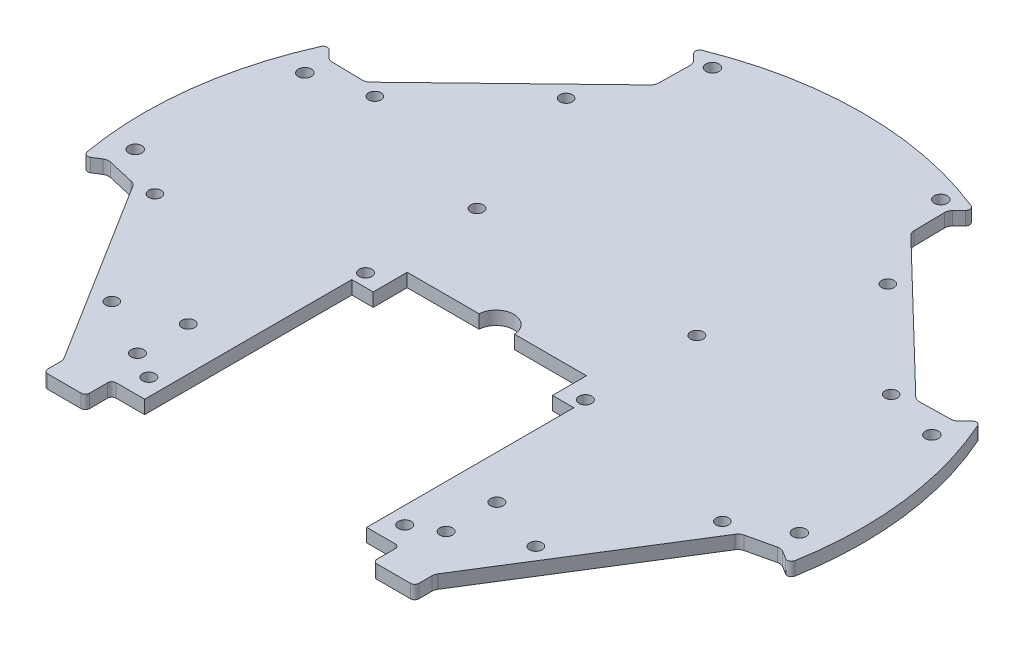
SolidWorks part; units mm, degrees
note: '?' marks a value the reader was unsure of.
material "6061 Alloy"
ref_plane "Front Plane" through (0, 0, 0) normal (0, 0, 1) x (1, 0, 0)
ref_plane "Top Plane" through (0, 0, 0) normal (0, 1, 0) x (1, 0, 0)
ref_plane "Right Plane" through (0, 0, 0) normal (1, 0, 0) x (0, 0, -1)
sketch "Sketch1" plane through (0, 0, 0) normal (0, 1, 0) x (1, 0, 0)
  line L0 (0, 0) -> (0, -59.55) construction
  line L1 (-83.4462, -16.178) -> (-71.2857, -8.5793) construction
  line L6 (0, 0) -> (-59.046, 61.1439) construction
  line L7 (0, 0) -> (-72.0841, -45.0431) construction
  line L8 (-33.174, 78.2591) -> (-23.2129, 67.9442) construction
  line L9 (-72.0841, -45.0431) -> (-70.388, -43.9833) construction
  line L10 (-70.388, -43.9833) -> (-84.9608, -20.662) construction
  line L11 (-84.9608, -20.662) -> (-72.2401, -12.7132) construction
  line L12 (-72.2401, -12.7132) -> (-43.0945, -59.3558) construction
  line L13 (-43.0945, -59.3558) -> (-55.8152, -67.3046) construction
  line L14 (-55.8152, -67.3046) -> (-70.388, -43.9833) construction
  line L21 (-59.046, 61.1439) -> (-57.6566, 59.7052)
  line L22 (-77.4385, 40.6021) -> (-37.8748, 78.8083) construction
  line L23 (-73.9694, 32.6911) -> (-77.0537, 35.885)
  line L24 (-37.8748, 78.8083) -> (-27.4549, 68.0182) construction
  line L25 (-27.4549, 68.0182) -> (-67.0186, 29.812) construction
  line L26 (-67.0186, 29.812) -> (-77.4385, 40.6021) construction
  line L27 (-43.0945, -64.8266) -> (-34, -64.8266)
  line L33 (-86.5505, -18.1178) -> (-71.2857, -8.5793) construction
  line L34 (0, 0) -> (0, 50000) construction
  line L35 (0, 0) -> (-50000, 0) construction
  line L36 (-60.6531, -59.55) -> (-19.8595, -59.55) construction
  line L38 (-67.0927, 25.57) -> (-79.5965, 38.5181) construction
  line L39 (-54.9774, -64.8266) -> (0, -64.8266) construction
  line L40 (-35.7168, 80.8923) -> (-23.2129, 67.9442) construction
  line L41 (-38.9606, -60.3102) -> (-54.2255, -69.8488) construction
  line L42 (-34, -59.55) -> (-19.8595, -59.55) construction
  line L43 (-43.0945, -64.8266) -> (-43.0945, -58.4123) construction
  line L45 (73.9694, 32.6911) -> (77.0537, 35.885)
  line L46 (-71.2857, -8.5793) -> (-38.9606, -60.3102) construction
  line L47 (83.4462, -16.178) -> (79.6809, -13.8252)
  line L48 (69.4846, -16.1792) -> (43.8945, -57.132)
  line L50 (43.0945, -64.8266) -> (34, -64.8266)
  line L51 (34, -59.55) -> (34, -64.8266)
  line L52 (0, 0) -> (72.0841, -45.0431) construction
  line L53 (0, 0) -> (59.046, 61.1439) construction
  line L54 (-30.0897, 75.0653) -> (-30.2847, 63.8954)
  line L55 (-62.7996, 32.4961) -> (-30.2847, 63.8954)
  line L56 (-30.0897, 75.0653) -> (-33.174, 78.2591)
  line L57 (73.9694, 32.6911) -> (77.0537, 35.885)
  line L58 (30.0897, 75.0653) -> (33.174, 78.2591)
  line L59 (-34, -59.55) -> (-34, -58.55)
  line L60 (62.7996, 32.4961) -> (30.2847, 63.8954)
  line L61 (-73.9694, 32.6911) -> (-62.7996, 32.4961)
  line L62 (-77.0537, 35.885) -> (-67.0927, 25.57) construction
  line L63 (-83.4462, -16.178) -> (-79.6809, -13.8252)
  line L64 (-79.6809, -13.8252) -> (-69.4846, -16.1792)
  line L65 (-69.4846, -16.1792) -> (-43.8945, -57.132)
  line L66 (-27.4549, 68.0182) -> (-23.2129, 67.9442) construction
  line L67 (-72.2401, -12.7132) -> (-71.2857, -8.5793) construction
  line L68 (30.0897, 75.0653) -> (30.2847, 63.8954)
  line L69 (73.9694, 32.6911) -> (62.7996, 32.4961)
  line L70 (-34, -59.55) -> (-34, -64.8266)
  line L71 (79.6809, -13.8252) -> (69.4846, -16.1792)
  line L72 (-34, -58.55) -> (-20, -58.55)
  line L73 (-20, -58.55) -> (-19.8595, -59.55)
  line L74 (-19.8595, -59.55) -> (19.8595, -59.55)
  line L75 (20, -58.55) -> (19.8595, -59.55)
  line L76 (34, -58.55) -> (20, -58.55)
  line L77 (34, -59.55) -> (34, -58.55)
  line L78 (-43.0945, -64.8266) -> (-43.8945, -64.8266)
  line L79 (-19.8595, -59.55) -> (0, -59.55) construction
  line L80 (-19.8595, -59.55) -> (34, -59.55) construction
  line L81 (-43.8945, -64.8266) -> (-43.8945, -57.132)
  line L82 (-43.0945, -58.4123) -> (-43.8945, -57.132) construction
  line L83 (43.8945, -64.8266) -> (43.8945, -57.132)
  line L84 (43.0945, -64.8266) -> (43.8945, -64.8266)
  line L97 (-23.2129, 67.9442) -> (-67.0927, 25.57) construction
  circle A0 centre (0, 0) radius 85 construction
  circle A1 centre (0, 0) radius 90 construction
  arc A51 (-77.0537, 35.885) -> (-83.4462, -16.178) centre (0, 0) ccw
  arc A52 (77.0537, 35.885) -> (83.4462, -16.178) centre (0, 0) cw
  arc A54 (-33.174, 78.2591) -> (33.174, 78.2591) centre (0, 0) cw
  point P29 (-31.6318, 76.6622)
  point P33 (-47.2368, 48.9151)
  point P34 (31.6318, 76.6622)
  point P35 (-57.6673, -36.0345)
  point P85 (-57.6566, 59.7052)
  dimension "D2" = 58
  dimension "D10" = 82
  dimension "D12" = 170
  dimension "D14" = 34
  dimension "D13" = 1
  dimension "D15" = 3
  dimension "D3" = 180
  dimension "D4" = 64.8266
  dimension "D5" = 44
  dimension "D6" = 15
  dimension "D7" = 55
  dimension "D8" = 59.55
  dimension "D9" = 2
  dimension "D11" = 2
  dimension "D16" = 7
  dimension "D17" = 7
  dimension "D18" = 0.5
  dimension "D19" = 1
  dimension "D20" = 14
  dimension "D21" = 0.8
extrude "Boss-Extrude4" add sketch "Sketch1" along normal mid plane 3.175
ref_point "Rear_Axle_Center (L)"
ref_axis "Rear_Axle_Proj (L)" through (46.5421, 0, -48.1958) along (0, 1, 0)?
ref_point "Front_Axle_Center (L)"
ref_axis "Front_Axle_Proj (L)" through (57.2432, 0, 35.7696) along (0, 1, 0)?
ref_point "Front_Axle_Center (R)"
ref_axis "Front_Axle_Proj (R)" through (-57.2432, 0, 35.7696) along (0, 1, 0)?
ref_point "Read_Axle_Center (R)"
ref_axis "Rear_Axle_Proj (R)" through (-46.5421, 0, -48.1958) along (0, 1, 0)?
sketch "Sketch17" plane through (0, 1.5875, 0) normal (0, 1, 0) x (1, 0, 0)
  line L0 (0, -54.55) -> (0, -59.55) construction
  line L1 (-19.8595, -59.55) -> (19.8595, -59.55) construction
  circle A0 centre (0, -54.55) radius 8.5
  dimension "D1" = 17
  dimension "D2" = 5
extrude "Boss-Extrude5" [suppressed] add sketch "Sketch17" against normal up to surface (3.175 mm away)
ref_plane "Plane1" through (0, 0, 10) normal (0, 0, 1) x (1, 0, 0)
hole_wizard "M3 Clearance Hole3" positions "Sketch18" profile "Sketch19" hole size "M3" standard "ANSI Metric" end condition through all
sketch "Sketch18" plane through (0, -1.5875, 0) normal (0, -1, 0) x (-1, 0, 0)
  line L0 (-36.5, -50) -> (-36.5, -38) construction
  line L3 (0, 0) -> (0, -38) construction
  line L4 (36.5, -50) -> (36.5, -38) construction
  line L6 (0, -38) -> (36.5, -38) construction
  line L8 (0, -38) -> (-36.5, -38) construction
  line L9 (-36.5, -44) -> (36.5, -44) construction
  line L10 (0, -44) -> (0, 0) construction
  point P1 (36.5, -50)
  point P3 (36.5, -38)
  point P5 (-36.5, -50)
  point P33 (-36.5, -38)
  dimension "D1" = 12
  dimension "D2" = 73
  dimension "D4" = 38
sketch "Sketch19" plane through (-36.5, -1.5875, 50) normal (1, 0, 0) x (0, 0, -1)
  line L0 (0, 0) -> (0, 3.175)
  line L1 (0, 3.175) -> (1.5, 3.175)
  line L2 (1.5, 3.175) -> (1.5, 0)
  line L5 (1.5, 0) -> (0, 0)
  line L11 (0, -6.35) -> (0, 107.95) construction
  dimension "Thru Hole Dia." = 3
  dimension "Thru Hole Depth" = 3.175
hole_wizard "M3 Clearance Hole1" positions "Sketch11" profile "Sketch12" hole size "M3" standard "ANSI Metric" end condition through all
sketch "Sketch11" plane through (0, 1.5875, 0) normal (0, 1, 0) x (1, 0, 0)
  line L0 (83.4462, -16.178) -> (79.6809, -13.8252) construction
  line L2 (73.9694, 32.6911) -> (77.0537, 35.885) construction
  line L4 (-73.9694, 32.6911) -> (-77.0537, 35.885) construction
  line L6 (0, 0) -> (0, -50000) construction
  line L7 (78.4111, 9.6277) -> (84.3664, 10.3589) construction
  line L10 (74.155, 27.2403) -> (78.5423, -8.4914) construction
  line L12 (78.4111, 9.6277) -> (76.3487, 9.3744) construction
  arc A7 (77.964, -12.7523) -> (72.563, 31.2347) centre (0, 0) ccw construction
  arc A13 (-77.964, -12.7523) -> (-72.563, 31.2347) centre (0, 0) cw construction
  arc A17 (83.4462, -16.178) -> (77.0537, 35.885) centre (0, 0) ccw construction
  point P34 (78.5423, -8.4914)
  point P66 (74.155, 27.2403)
  point P70 (-74.155, 27.2403)
  point P71 (-78.5423, -8.4914)
  dimension "D1" = 6
  dimension "D2" = 36
sketch "Sketch12" plane through (-78.5423, 1.5875, 8.4914) normal (1, 0, 0) x (0, 0, 1)
  line L0 (0, 0) -> (0, 3.175)
  line L1 (0, 3.175) -> (1.55, 3.175)
  line L2 (1.55, 3.175) -> (1.55, 0)
  line L5 (1.55, 0) -> (0, 0)
  line L11 (0, -6.35) -> (0, 107.95) construction
  dimension "Thru Hole Dia." = 3.1
  dimension "Thru Hole Depth" = 3.175
hole_wizard "M3 Clearance Hole4" positions "Sketch9" profile "Sketch10" hole size "M3" standard "ANSI Metric" end condition through all
sketch "Sketch9" plane through (0, -1.5875, 0) normal (0, -1, 0) x (-1, 0, 0)
  line L0 (0, 0) -> (0, 63.4318) construction
  line L1 (-38.0437, 52.9272) -> (38.0437, 52.9272) construction
  line L3 (61.0625, 30.6981) -> (-61.0625, 30.6981) construction
  line L4 (-67.0993, -15.2789) -> (67.0993, -15.2789) construction
  line L5 (50.1419, -42.4164) -> (-50.1419, -42.4164) construction
  line L6 (-61.0625, 30.6981) -> (-38.0437, 52.9272) construction
  line L7 (38.0437, 52.9272) -> (61.0625, 30.6981) construction
  line L8 (67.0993, -15.2789) -> (50.1419, -42.4164) construction
  line L9 (-50.1419, -42.4164) -> (-67.0993, -15.2789) construction
  line L10 (0, 0) -> (-44.8055, 46.3974) construction
  line L11 (0, 0) -> (44.8055, 46.3974) construction
  line L12 (0, 0) -> (-96.9468, 0) construction
  line L14 (-55.1231, -34.4448) -> (0, 0) construction
  line L15 (0, 0) -> (55.1231, -34.4448) construction
  line L18 (-69.4846, -16.1792) -> (-43.8945, -57.132) construction
  line L19 (-62.7996, 32.4961) -> (-30.2847, 63.8954) construction
  point P0 (-67.0993, -15.2789)
  point P2 (-50.1419, -42.4164)
  point P9 (-61.0625, 30.6981)
  point P11 (-38.0437, 52.9272)
  point P30 (50.1419, -42.4164)
  point P31 (67.0993, -15.2789)
  point P32 (38.0437, 52.9272)
  point P33 (61.0625, 30.6981)
  dimension "D9" = 46
  dimension "D10" = 46
  dimension "D11" = 32
  dimension "D12" = 32
  dimension "D7" = 58
  dimension "D5" = 32
  dimension "D6" = 2.5
  dimension "D8" = 9.4
  dimension "D2" = 44
  dimension "D3" = 32
  dimension "D4" = 2.5
  dimension "D13" = 9.4
sketch "Sketch10" plane through (67.0993, -1.5875, 15.2789) normal (1, 0, 0) x (0, 0, -1)
  line L0 (0, 0) -> (0, 3.175)
  line L1 (0, 3.175) -> (1.475, 3.175)
  line L2 (1.475, 3.175) -> (1.475, 0)
  line L5 (1.475, 0) -> (0, 0)
  line L11 (0, -6.35) -> (0, 107.95) construction
  dimension "Thru Hole Dia." = 2.95
  dimension "Thru Hole Depth" = 3.175
hole_wizard "M3 Clearance Hole2" positions "Sketch13" profile "Sketch14" hole size "M3" standard "ANSI Metric" end condition through all
sketch "Sketch13" plane through (0, 1.5875, 0) normal (0, 1, 0) x (1, 0, 0)
  line L0 (0, 0) -> (0, 85) construction
  line L2 (-24, 47) -> (-24, 81) construction
  line L3 (-24, 47) -> (24, 47) construction
  line L4 (-24, 81) -> (24, 81) construction
  line L5 (24, 47) -> (24, 81) construction
  line L6 (-24, 47) -> (24, 81) construction
  line L7 (-24, 81) -> (24, 47) construction
  line L8 (-38.0437, 52.9272) -> (-61.0625, 30.6981) construction
  line L10 (-36.307, 51.1289) -> (-59.3259, 28.8998) construction
  line L11 (-16.3488, 39.8187) -> (-31.6313, 55.6441) construction
  line L12 (-16.3488, 39.8187) -> (-48.7191, 8.559) construction
  line L13 (-31.6313, 55.6441) -> (-64.0016, 24.3845) construction
  line L14 (-48.7191, 8.559) -> (-64.0016, 24.3845) construction
  line L15 (-16.3488, 39.8187) -> (-64.0016, 24.3845) construction
  line L16 (-31.6313, 55.6441) -> (-48.7191, 8.559) construction
  line L17 (-49.5531, 41.8127) -> (-40.1752, 32.1016) construction
  line L18 (-27, 76.4978) -> (-27, 80.5978) construction
  arc A0 (33.174, 78.2591) -> (-33.174, 78.2591) centre (0, 0) ccw construction
  circle A1 centre (-16.2162, 44) radius 3 construction
  circle A2 centre (-27, 76.4978) radius 3 construction
  point P65 (0, 64)
  point P181 (-27, 76.4978)
  point P184 (27, 76.4978)
  dimension "D7" = 6
  dimension "D1" = 48
  dimension "D2" = 34
  dimension "D3" = 4
  dimension "D5" = 45
  dimension "D6" = 22
  dimension "D8" = 4.1
  dimension "D4" = 2.5
sketch "Sketch14" plane through (27, 1.5875, -76.4978) normal (1, 0, 0) x (0, 0, 1)
  line L0 (0, 0) -> (0, 3.175)
  line L1 (0, 3.175) -> (1.55, 3.175)
  line L2 (1.55, 3.175) -> (1.55, 0)
  line L5 (1.55, 0) -> (0, 0)
  line L11 (0, -6.35) -> (0, 107.95) construction
  dimension "Thru Hole Dia." = 3.1
  dimension "Thru Hole Depth" = 3.175
hole_wizard "M3 Clearance Hole5" [suppressed] positions "Sketch24" profile "Sketch25" hole size "M3" standard "ANSI Metric"
sketch "Sketch24" plane through (0, 1.5875, 0) normal (0, 1, 0) x (1, 0, 0)
  line L1 (-11, -4.4) -> (11, -4.4) construction
  line L2 (11, -4.4) -> (11, -36.4) construction
  line L3 (11, -36.4) -> (-11, -36.4) construction
  line L4 (-11, -36.4) -> (-11, -4.4) construction
  line L7 (-11, 37.6) -> (11, 37.6) construction
  line L8 (0, -4.4) -> (0, 0) construction
  line L9 (0, 0) -> (0, 37.6) construction
  point P8 (-11, -4.4)
  point P10 (11, -4.4)
  point P12 (11, -36.4)
  point P14 (-11, -36.4)
  point P42 (-11, 37.6)
  point P45 (11, 37.6)
  dimension "D1" = 22
  dimension "D2" = 32
  dimension "D3" = 4.4
  dimension "D4" = 42
sketch "Sketch25" plane through (-11, 1.5875, 4.4) normal (1, 0, 0) x (0, 0, 1)
  line L0 (0, 0) -> (0, 3.175)
  line L1 (0, 3.175) -> (1.5, 3.175)
  line L2 (1.5, 3.175) -> (1.5, 0)
  line L5 (1.5, 0) -> (0, 0)
  line L11 (0, -6.35) -> (0, 107.95) construction
  dimension "Thru Hole Dia." = 3
  dimension "Thru Hole Depth" = 3.175
sketch "Sketch20" plane through (0, 1.5875, 0) normal (0, 1, 0) x (1, 0, 0)
  line L0 (-16.1485, 44) -> (-16.1485, 39) construction
  line L1 (-14.6485, 44) -> (-14.6485, 39)
  line L2 (-17.6485, 44) -> (-17.6485, 39)
  line L3 (0, 0) -> (0, 85) construction
  line L5 (16.1485, 44) -> (16.1485, 39) construction
  line L6 (14.6485, 44) -> (14.6485, 39)
  line L7 (17.6485, 44) -> (17.6485, 39)
  arc A0 (-14.6485, 44) -> (-17.6485, 44) centre (-16.1485, 44) ccw
  arc A1 (-17.6485, 39) -> (-14.6485, 39) centre (-16.1485, 39) ccw
  arc A5 (33.174, 78.2591) -> (-33.174, 78.2591) centre (0, 0) ccw construction
  arc A7 (14.6485, 44) -> (17.6485, 44) centre (16.1485, 44) cw
  arc A8 (17.6485, 39) -> (14.6485, 39) centre (16.1485, 39) cw
  point P2 (-16.1485, 41.5)
  point P16 (16.1485, 41.5)
  dimension "D1" = 44
  dimension "D2" = 3
  dimension "D3" = 5
  dimension "D4" = 16.1485
extrude "Cut-Extrude1" [suppressed] cut sketch "Sketch20" against normal through all
sketch "Sketch22" plane through (0, 1.5875, 0) normal (0, 1, 0) x (1, 0, 0)
  line L0 (-56.6896, -36.6556) -> (-58.0464, -37.5035) construction
  line L1 (-69.4846, -16.1792) -> (-43.8945, -57.132) construction
  line L3 (30.2452, 66.1578) -> (65.062, 32.5356)
  line L4 (71.6894, -15.6702) -> (43.8945, -60.1514)
  line L5 (-19.8595, -59.55) -> (19.8595, -59.55) construction
  line L6 (-43.8945, -64.8266) -> (-43.8945, -57.132) construction
  line L28 (-30.2452, 66.1578) -> (-65.062, 32.5356)
  line L29 (-71.6894, -15.6702) -> (-43.8945, -60.1514)
  line L30 (-79.6809, -13.8252) -> (-69.4846, -16.1792) construction
  line L31 (0, 85) -> (0, -59.55) construction
  line L32 (-46.5421, 48.1958) -> (-47.6536, 49.3467) construction
  line L37 (-20, -58.55) -> (-19.8595, -59.55)
  line L38 (-20, -58.55) -> (-19.8595, -59.55)
  line L40 (-43.8945, -57.132) -> (-43.8945, -64.8266)
  line L41 (-43.8945, -57.132) -> (-43.8945, -64.8266)
  line L43 (43.8945, -64.8266) -> (43.8945, -57.132)
  line L44 (43.8945, -64.8266) -> (43.8945, -57.132)
  line L56 (-19.8595, -59.55) -> (19.8595, -59.55)
  line L58 (19.8595, -59.55) -> (20, -58.55)
  line L59 (20, -58.55) -> (34, -58.55)
  line L60 (34, -58.55) -> (34, -64.8266)
  line L61 (34, -64.8266) -> (43.8945, -64.8266)
  line L63 (43.8945, -57.132) -> (69.4846, -16.1792)
  line L64 (69.4846, -16.1792) -> (79.6809, -13.8252)
  line L65 (79.6809, -13.8252) -> (83.4462, -16.178)
  line L66 (77.0537, 35.885) -> (73.9694, 32.6911)
  line L67 (73.9694, 32.6911) -> (62.7996, 32.4961)
  line L68 (62.7996, 32.4961) -> (30.2847, 63.8954)
  line L69 (30.2847, 63.8954) -> (30.0897, 75.0653)
  line L70 (30.0897, 75.0653) -> (33.174, 78.2591)
  line L71 (-33.174, 78.2591) -> (-30.0897, 75.0653)
  line L72 (-30.0897, 75.0653) -> (-30.2847, 63.8954)
  line L73 (-30.2847, 63.8954) -> (-62.7996, 32.4961)
  line L74 (-62.7996, 32.4961) -> (-73.9694, 32.6911)
  line L75 (-73.9694, 32.6911) -> (-77.0537, 35.885)
  line L76 (-83.4462, -16.178) -> (-79.6809, -13.8252)
  line L77 (-79.6809, -13.8252) -> (-69.4846, -16.1792)
  line L78 (-69.4846, -16.1792) -> (-43.8945, -57.132)
  line L80 (-43.8945, -64.8266) -> (-34, -64.8266)
  line L81 (-34, -64.8266) -> (-34, -58.55)
  line L82 (-34, -58.55) -> (-20, -58.55)
  line L84 (-19.8595, -59.55) -> (19.8595, -59.55)
  line L86 (19.8595, -59.55) -> (20, -58.55)
  line L87 (20, -58.55) -> (34, -58.55)
  line L88 (34, -58.55) -> (34, -64.8266)
  line L89 (34, -64.8266) -> (43.8945, -64.8266)
  line L91 (43.8945, -57.132) -> (69.4846, -16.1792)
  line L92 (69.4846, -16.1792) -> (79.6809, -13.8252)
  line L93 (79.6809, -13.8252) -> (83.4462, -16.178)
  line L94 (77.0537, 35.885) -> (73.9694, 32.6911)
  line L95 (73.9694, 32.6911) -> (62.7996, 32.4961)
  line L96 (62.7996, 32.4961) -> (30.2847, 63.8954)
  line L97 (30.2847, 63.8954) -> (30.0897, 75.0653)
  line L98 (30.0897, 75.0653) -> (33.174, 78.2591)
  line L99 (-33.174, 78.2591) -> (-30.0897, 75.0653)
  line L100 (-30.0897, 75.0653) -> (-30.2847, 63.8954)
  line L101 (-30.2847, 63.8954) -> (-62.7996, 32.4961)
  line L102 (-62.7996, 32.4961) -> (-73.9694, 32.6911)
  line L103 (-73.9694, 32.6911) -> (-77.0537, 35.885)
  line L104 (-83.4462, -16.178) -> (-79.6809, -13.8252)
  line L105 (-79.6809, -13.8252) -> (-69.4846, -16.1792)
  line L106 (-69.4846, -16.1792) -> (-43.8945, -57.132)
  line L108 (-43.8945, -64.8266) -> (-34, -64.8266)
  line L109 (-34, -64.8266) -> (-34, -58.55)
  line L110 (-34, -58.55) -> (-20, -58.55)
  arc A9 (83.4462, -16.178) -> (77.0537, 35.885) centre (0, 0) ccw
  arc A10 (33.174, 78.2591) -> (-33.174, 78.2591) centre (0, 0) ccw
  arc A11 (-77.0537, 35.885) -> (-83.4462, -16.178) centre (0, 0) ccw
  arc A13 (83.4462, -16.178) -> (77.0537, 35.885) centre (0, 0) ccw
  arc A14 (33.174, 78.2591) -> (-33.174, 78.2591) centre (0, 0) ccw
  arc A15 (-77.0537, 35.885) -> (-83.4462, -16.178) centre (0, 0) ccw
  dimension "D2" = 1.6
  dimension "D1" = 0
extrude "Boss-Extrude6" add sketch "Sketch22" against normal up to surface (3.175 mm away) up to face at (-27, -1.5875, -74.9478)
fillet "Fillet1" radius 2 14 edges at (-30.0897, 0, -75.0653) (30.0897, 0, -75.0653) (-79.6809, 0, 13.8252) (79.6809, 0, 13.8252) (73.9694, 0, -32.6911) (-73.9694, 0, -32.6911) (65.062, 0, -32.5356) (30.2452, 0, -66.1578) (71.6894, 0, 15.6702) (-71.6894, 0, 15.6702) (-65.062, 0, -32.5356) (-30.2452, 0, -66.1578) (43.8945, 0, 60.1514) (-43.8945, 0, 60.1514)
fillet "Fillet3" radius 1 12 edges at (-77.0537, 0, -35.885) (77.0537, 0, -35.885) (83.4462, 0, 16.178) (34, 0, 64.8266) (-34, 0, 64.8266) (-33.174, 0, -78.2591) (33.174, 0, -78.2591) (-83.4462, 0, 16.178) (34, 0, 58.55) (-34, 0, 58.55) (-43.8945, 0, 64.8266) (43.8945, 0, 64.8266)
sketch "Sketch23" [suppressed] plane through (0, 3.175, 0) normal (0, 1, 0) x (1, 0, 0)
  circle A0 centre (0, -53.55) radius 4.95
  dimension "D1" = 9.9
fillet "Fillet6" radius 0.5 4 edges at (20, 0, 58.55) (19.8595, 0, 59.55) (-20, 0, 58.55) (-19.8595, 0, 59.55)
sketch "Sketch28" plane through (0, 1.5875, 0) normal (0, 1, 0) x (1, 0, 0)
  line L0 (-19.4248, -59.55) -> (19.4248, -59.55) construction
  line L1 (-19.4248, -59.55) -> (19.4248, -59.55) construction
  line L2 (-26.25, -59.55) -> (26.25, -59.55)
  line L3 (-26.25, -59.55) -> (-26.25, -9.55)
  line L4 (26.25, -59.55) -> (26.25, -9.55)
  line L5 (-26.25, -9.55) -> (26.25, -9.55)
  line L6 (0, -1.7) -> (0, -77.8833) construction
  line L7 (-21, -1.7) -> (-21, -9.55) construction
  line L8 (21, -1.7) -> (4, -1.7) construction
  line L9 (21, -1.7) -> (21, -9.55) construction
  line L10 (-4, -1.7) -> (-21, -1.7) construction
  line L11 (21.2, -1.5) -> (21.2, -9.55)
  line L12 (21.2, -1.5) -> (4.1952, -1.5)
  line L13 (-4.1952, -1.5) -> (-21.2, -1.5)
  line L14 (-21.2, -1.5) -> (-21.2, -9.55)
  arc A0 (19.4248, -59.55) -> (19.9199, -59.1196) centre (19.4248, -59.05) ccw construction
  arc A1 (4, -1.7) -> (-4, -1.7) centre (0, -1.7) ccw construction
  arc A2 (4.1952, -1.5) -> (-4.1952, -1.5) centre (0, -1.7) ccw
  point P11 (0, -59.55)
  point P16 (0, -9.55)
  point P23 (0, -1.7)
  dimension "D4" = 4
  dimension "D1" = 52.5
  dimension "D2" = 50
  dimension "D3" = 17
  dimension "D5" = 7.85
extrude "Cut-Extrude4" cut sketch "Sketch28" against normal blind 10 contours L8 A1 L10 L7 L5 L9 | L5 L3 L2 L4
extrude "Cut-Extrude2" [suppressed] cut sketch "Sketch23" against normal through all
sketch "Sketch26" [suppressed] plane through (0, 3.175, 0) normal (0, 1, 0) x (1, 0, 0)
  line L0 (0, 0) -> (0, 50) construction
  line L1 (-92.5, 5) -> (92.5, 5)
  line L2 (-92.5, 5) -> (-92.5, 95)
  line L3 (-92.5, 95) -> (92.5, 95)
  line L4 (92.5, 5) -> (92.5, 95)
  line L5 (-92.5, 5) -> (92.5, 95) construction
  line L6 (-92.5, 95) -> (92.5, 5) construction
  point P0 (0, 50)
  dimension "D1" = 90
  dimension "D2" = 185
  dimension "D3" = 5
extrude "Cut-Extrude3" [suppressed] cut sketch "Sketch26" against normal through all
fillet "Fillet4" [suppressed] radius 5
sketch "Sketch29" plane through (0, 1.5875, 0) normal (0, 1, 0) x (1, 0, 0)
  line L0 (-33, -58.55) -> (-26.25, -58.55) construction
  line L1 (0, -81.301) -> (0, 102.6168) construction
  line L2 (-26.25, -9.55) -> (-26.25, -58.55) construction
  line L3 (-26.25, -53.55) -> (-32.5626, -53.55) construction
  line L4 (-26.25, -53.55) -> (-30.25, -53.55)
  circle A0 centre (30.25, -53.55) radius 1.5
  circle A1 centre (-30.25, -53.55) radius 1.5
  dimension "D5" = 3
  dimension "D1" = 5
  dimension "D2" = 30.25
extrude "Cut-Extrude5" cut sketch "Sketch29" against normal blind 10
sketch "Sketch31" plane through (0, 1.5875, 0) normal (0, 1, 0) x (1, 0, 0)
  line L0 (26.25, -9.55) -> (21.2, -9.55) construction
  line L1 (0, 35.8655) -> (0, -81.8862) construction
  line L2 (-26, -6.55) -> (-26, 19.8) construction
  circle A0 centre (-26, -6.55) radius 1.5
  circle A1 centre (26, -6.55) radius 1.5
  circle A2 centre (-26, 19.8) radius 1.5
  circle A3 centre (26, 19.8) radius 1.5
  point P10 (0, 0)
  point P11 (0, 0)
  dimension "D3" = 3
  dimension "D1" = 52
  dimension "D2" = 3
  dimension "D4" = 26.35
extrude "Cut-Extrude7" cut sketch "Sketch31" against normal blind 10
sketch "Sketch32" plane through (0, 1.5875, 0) normal (0, 1, 0) x (1, 0, 0)
  line L0 (-43.6016, -64.5337) -> (43.6016, -64.5337)
  line L1 (-43.6016, -64.5337) -> (-43.6016, 20.2064)
  line L2 (43.6016, -64.5337) -> (43.6016, 20.2064)
  line L3 (-43.6016, 20.2064) -> (43.6016, 20.2064)
  arc A0 (-43.8945, -63.8266) -> (-42.8945, -64.8266) centre (-42.8945, -63.8266) ccw construction
  arc A1 (42.8945, -64.8266) -> (43.8945, -63.8266) centre (42.8945, -63.8266) ccw construction
extrude "Cut-Extrude8" [suppressed] cut sketch "Sketch32" against normal blind 10 flip side to cut
sketch "Sketch33" [suppressed] plane through (0, -1.5875, 0) normal (0, -1, 0) x (1, 0, 0)
  line L0 (-43.6016, 64.5337) -> (-34.2929, 64.5337)
  line L1 (-43.6016, 64.5337) -> (-43.6016, 54.5337)
  line L2 (-34.2929, 64.5337) -> (-34.2929, 54.5337)
  line L3 (-43.6016, 54.5337) -> (-34.2929, 54.5337)
  line L4 (43.6016, 64.5337) -> (34.2929, 64.5337)
  line L5 (43.6016, 64.5337) -> (43.6016, 54.5337)
  line L6 (34.2929, 64.5337) -> (34.2929, 54.5337)
  line L7 (43.6016, 54.5337) -> (34.2929, 54.5337)
  line L9 (-43.6016, -20.2064) -> (-33.6016, -20.2064)
  line L10 (-43.6016, -20.2064) -> (-43.6016, -10.2064)
  line L11 (-43.6016, -10.2064) -> (-33.6016, -10.2064)
  line L12 (-33.6016, -20.2064) -> (-33.6016, -10.2064)
  line L13 (43.6016, -20.2064) -> (33.6016, -20.2064)
  line L14 (43.6016, -20.2064) -> (43.6016, -10.2064)
  line L15 (43.6016, -10.2064) -> (33.6016, -10.2064)
  line L16 (33.6016, -20.2064) -> (33.6016, -10.2064)
  dimension "D1" = 10
  dimension "D2" = 10
  dimension "D3" = 10
  dimension "D4" = 10
  dimension "D5" = 10
  dimension "D6" = 10
extrude "Boss-Extrude7" [suppressed] add sketch "Sketch33" along normal blind 5
equation "\"D3@Sketch9\"=\"D5@Sketch9\""
equation "\"D4@Sketch9\"=\"D6@Sketch9\""
equation "\"D13@Sketch9\"=\"D8@Sketch9\""
equation "\"D1@Sketch28\"=54.000000mm-1.5"
